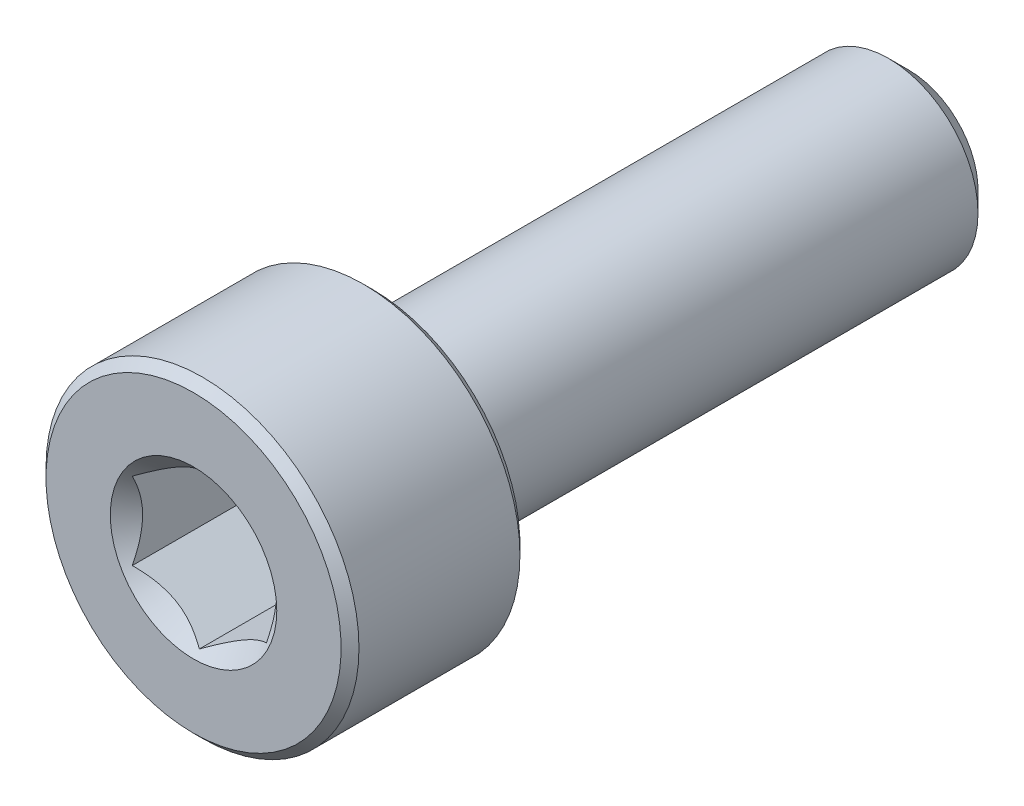
SolidWorks part; units mm, degrees
material "Alloy Steel (SS)"
ref_plane "Front Plane" through (0, 0, 0) normal (0, 0, 1) x (1, 0, 0)
ref_plane "Top Plane" through (0, 0, 0) normal (0, 1, 0) x (1, 0, 0)
ref_plane "Right Plane" through (0, 0, 0) normal (1, 0, 0) x (0, 0, -1)
sketch "Sketch1" plane through (0, 0, 0) normal (1, 0, 0) x (0, 0, -1)
  line L0 (-8, 0) -> (8, 0) construction
  line L1 (8, 0) -> (8, 1.5453) construction
  line L2 (8, 1.5453) -> (7.5453, 2) construction
  line L3 (7.5453, 2) -> (7.475, 2) construction
  line L4 (7.475, 2) -> (-4, 2) construction
  line L5 (-4, 2) -> (-4, 3.5) construction
  line L6 (-4, 3.5) -> (-8, 3.5) construction
  line L7 (-8, 3.5) -> (-8, 0) construction
  line L8 (8, 1.5453) -> (8, 2) construction
  line L9 (7.9562, 2.0758) -> (8.3062, 1.4696) construction
  line L10 (8.3062, 1.4696) -> (8.6562, 2.0758) construction
  line L11 (8.6562, 2.0758) -> (7.9562, 2.0758) construction
  line L12 (8.3062, 2.0758) -> (8.3062, 2) construction
  line L13 (8.3062, 1.4696) -> (8.3062, 1.5453) construction
  line L14 (8.2625, 1.5453) -> (8.35, 1.5453) construction
  line L15 (8, 2) -> (8.6125, 2) construction
  line L16 (7.9781, 2.0379) -> (8.6344, 2.0379) construction
  line L17 (8, 0) -> (8, -2) construction
  line L18 (-4.2, 3.5) -> (-4, 3.3) construction
  line L19 (-7.8, 3.5) -> (-8, 3.3) construction
  line L20 (-4, 2) -> (-4, 0) construction
  line L21 (-4, 1) -> (0, 1) construction
  line L22 (0, 1) -> (4, 1) construction
  line L23 (4, 1) -> (8, 1) construction
  line L24 (0, 1) -> (0, 2) construction
  line L25 (0, 2) -> (0, 3.5) construction
  line L26 (4, 1) -> (4, 3.5) construction
  point P0 (-8, 1.5)
  point P3 (6.25, 2)
  point P4 (0, 0)
  point P18 (4, 2)
  point P22 (8.3062, 1.5453)
  point P24 (7.475, 2)
  point P25 (8.3062, 2)
  point P28 (8.3062, 2.0379)
  point P29 (6.25, -2)
  point P30 (0, 2)
  point P31 (-6, 3.5)
  point P37 (-4.7, 3.5)
  point P38 (-7.7, 3.5)
  point P45 (0, 1)
  point P46 (4, 1)
  dimension "D2" = 0.0875
  dimension "D7" = 0.2
  dimension "D8" = 0.2
  dimension "D9" = 0.2
  dimension "D10" = 0.1
  dimension "D11" = 0.5
  dimension "Drive Size" = 3
  dimension "Head Diameter" = 7
  dimension "Head Height" = 4
  dimension "Thread Pitch" = 0.7
  dimension "Thread Dia" = 4
  dimension "Length" = 12
  dimension "D12" = 0.525
  dimension "D4" = 1.75
  dimension "D3" = 45
sketch "Sketch2" plane through (0, 0, 0) normal (1, 0, 0) x (0, 0, -1)
  line L0 (-8, 0) -> (-8, 3.3)
  line L1 (-7.8, 3.5) -> (-4.2, 3.5)
  line L2 (-4, 3.3) -> (-4, 2.2)
  line L4 (7.5453, 2) -> (8, 1.5453)
  line L5 (8, 1.5453) -> (8, 0)
  line L6 (-4, 3.5) -> (-8, 3.5) construction
  line L7 (8, 0) -> (-8, 0)
  line L8 (-7.8, 3.5) -> (-8, 3.3) construction
  line L10 (-7.8, 3.5) -> (-8, 3.3)
  line L14 (-4.2, 3.5) -> (-4, 3.3) construction
  line L16 (-4.2, 3.5) -> (-4, 3.3)
  line L17 (-4, 2) -> (-4, 3.5) construction
  line L19 (-3.8, 2) -> (7.5453, 2)
  line L20 (7.475, 2) -> (-4, 2) construction
  arc A1 (-4, 2.2) -> (-3.8, 2) centre (-3.8, 2.2) ccw
  dimension "D3" = 0.2
revolve "Revolve1" add sketch "Sketch2" angle 360 about L7
sketch "Sketch3" plane through (0, 0, 8) normal (0, 0, 1) x (1, 0, 0)
  line L1 (1.5, -0.866) -> (1.5, 0.866)
  line L2 (1.5, 0.866) -> (0, 1.7321)
  line L3 (0, 1.7321) -> (-1.5, 0.866)
  line L4 (-1.5, 0.866) -> (-1.5, -0.866)
  line L5 (-1.5, -0.866) -> (0, -1.7321)
  line L6 (0, -1.7321) -> (1.5, -0.866)
  circle A0 centre (0, 0) radius 1.5 construction
  circle A1 centre (0, 0) radius 3.5 construction
  circle A2 centre (0, 0) radius 3.5 construction
  circle A3 centre (0, 0) radius 1.7321 construction
  point P13 (0, 0)
  dimension "D1" = 3.4641
extrude "Cut-Extrude1" cut sketch "Sketch3" against normal offset from surface (3 mm away) 1 up to face at (0, 3.3, 4)
sketch "Sketch4" plane through (0, 0, 8) normal (0, 0, 1) x (1, 0, 0)
  circle A0 centre (0, 0) radius 1.862
  dimension "D1" = 3.7239
extrude "Cut-Extrude2" cut sketch "Sketch4" against normal up to vertex (2 mm away) draft 45 up to point (0, 3.5, 6)
sketch "Sketch11" plane through (0, 0, 0) normal (1, 0, 0) x (0, 0, -1)
  line L0 (-8, 0) -> (8, 0) construction
  line L1 (-8, 0) -> (8, 0) construction
  line L2 (-1.75, 0) -> (-1.75, 2) construction
  line L3 (7.475, 2) -> (-4, 2) construction
  line L4 (5.75, 0) -> (5.75, 2) construction
  line L6 (8, 1.5453) -> (8, 2) construction
  point P2 (-1.75, 0)
  point P3 (5.75, 0)
  dimension "D1" = 2.25
  dimension "D2" = 2.25
sketch "Sketch6" [suppressed] plane through (0, 0, -8) normal (0, 0, -1) x (-1, 0, 0)
  circle A0 centre (0, 0) radius 2
curve "Helix/Spiral1" [suppressed] pitch 0.7 height 12.7 turns 18.1429
sketch "Sketch10" [suppressed] plane through (0, 0, 0) normal (1, 0, 0) x (0, 0, -1)
  line L0 (-3.8, -3.5) -> (-3.8, 3.5)
  line L5 (-8, 0) -> (8, 0) construction
  line L6 (-3.8, 2) -> (-3.8, -2) construction
  point P3 (-3.8, 0)
split "Split1" [suppressed] bodies to split 106
sketch "Sketch7" [suppressed] plane through (0, 0, 0) normal (1, 0, 0) x (0, 0, -1)
  line L0 (7.9781, 2.0379) -> (8.6344, 2.0379)
  line L1 (8.6344, 2.0379) -> (8.35, 1.5453)
  line L2 (8.35, 1.5453) -> (8.2625, 1.5453)
  line L3 (8.2625, 1.5453) -> (7.9781, 2.0379)
sweep "Cut-Sweep1" [suppressed] cut profiles "Sketch7" path "Helix/Spiral1"
sketch "Sketch8" [suppressed] plane through (0, 0, 0) normal (1, 0, 0) x (0, 0, -1)
  line L0 (-4, 0) -> (-4, 2)
  line L1 (-3.8, -2) -> (-3.8, 2) construction
  line L2 (-4, 2) -> (-3.8, 2)
  line L4 (-3.8, 2) -> (-2.6453, 0)
  line L5 (-2.6453, 0) -> (-4, 0)
  line L6 (7.475, 2) -> (-4, 2) construction
  line L7 (-8, 0) -> (8, 0) construction
  dimension "D1" = 60
revolve "Revolve2" [suppressed] add sketch "Sketch8" angle 360 about L5
equation "\"D2@Sketch1\" = \"Thread Pitch@Sketch1\" / 8"
equation "\"D4@Helix/Spiral1\" = \"Thread Pitch@Sketch1\""
equation "\"D7@Sketch1\" = \"Head Height@Sketch1\" * .05"
equation "\"D8@Sketch1\"=\"D7@Sketch1\""
equation "\"D9@Sketch1\"=\"D7@Sketch1\""
equation "\"D10@Sketch1\"=\"D7@Sketch1\"/2"
equation "\"D11@Sketch1\"=\"D10@Sketch1\"*5"
equation "\"D4@Sketch1\"=\"Thread Pitch@Sketch1\"*2.5"
equation "\"D12@Sketch1\"=\"Thread Pitch@Sketch1\"*.75"
equation "\"D3@Helix/Spiral1\"=\"Length@Sketch1\"+\"Thread Pitch@Sketch1\""
equation "\"D3@Sketch2\"=\"Thread Dia@Sketch1\"*0.05"
equation "\"D1@Sketch11\"=\"Length@Sketch1\"*0.1875"
equation "\"D2@Sketch11\"=\"D1@Sketch11\""
equation "\"D1@Sketch4\"=\"D1@Sketch3\"*1.075"
